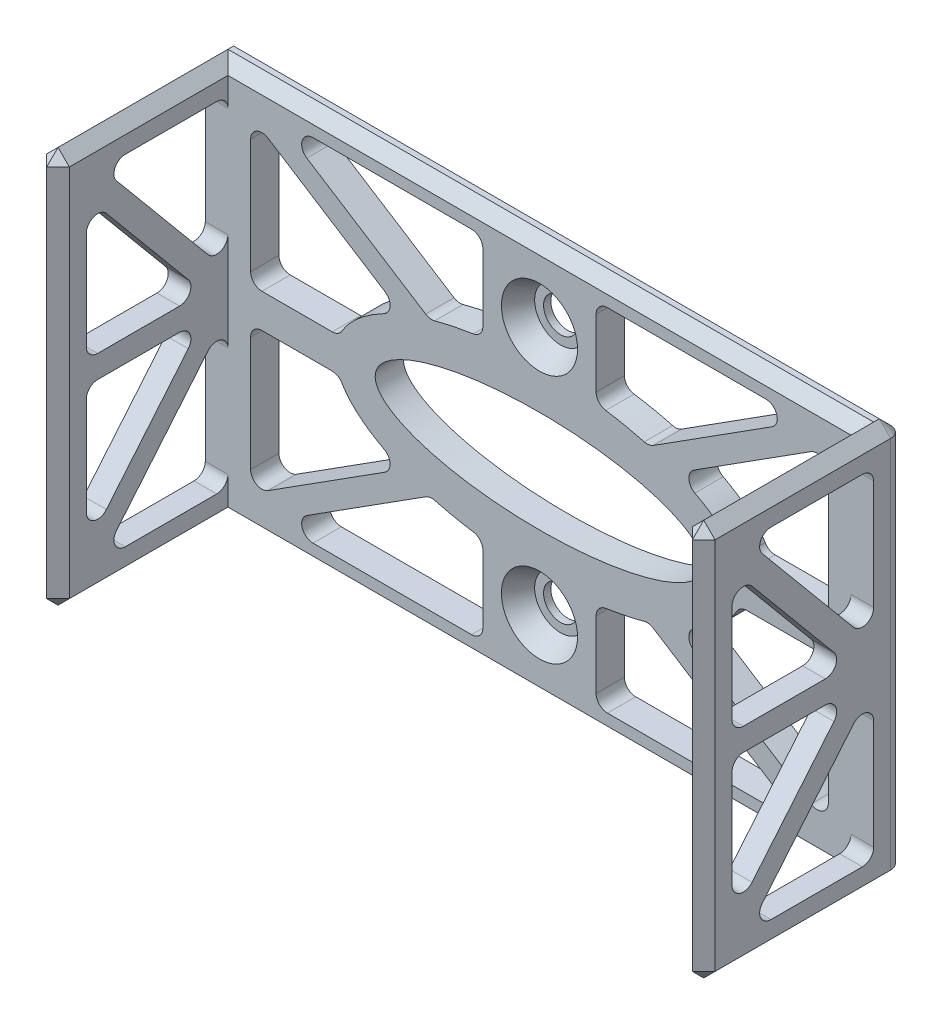
SolidWorks part; units mm, degrees
material "6061-T6 (SS)"
ref_plane "Front Plane" through (0, 0, 0) normal (0, 0, 1) x (1, 0, 0)
ref_plane "Top Plane" through (0, 0, 0) normal (0, 1, 0) x (1, 0, 0)
ref_plane "Right Plane" through (0, 0, 0) normal (1, 0, 0) x (0, 0, -1)
sketch "Sketch1" plane through (0, 0, 0) normal (0, 0, 1) x (1, 0, 0)
  line L1 (-55, 35) -> (55, 35)
  line L2 (-55, 35) -> (-55, -35)
  line L3 (-55, -35) -> (55, -35)
  line L4 (55, 35) -> (55, -35)
  line L5 (-55, 35) -> (55, -35) construction
  line L6 (-55, -35) -> (55, 35) construction
  circle A0 centre (0, 22) radius 3
  circle A1 centre (0, -22) radius 3
  point P0 (0, 0)
  dimension "D4" = 6
  dimension "D5" = 6
  dimension "D1" = 70
  dimension "D2" = 110
  dimension "D3" = 13
  dimension "D6" = 13
extrude "Boss-Extrude1" add sketch "Sketch1" along normal blind 5
sketch "Sketch2" plane through (0, 0, 5) normal (0, 0, 1) x (1, 0, 0)
  circle A0 centre (0, 22) radius 6.72
  circle A1 centre (0, -22) radius 6.72
  dimension "D1" = 13.44
  dimension "D2" = 13.44
extrude "Cut-Extrude1" cut sketch "Sketch2" against normal blind 3.72 draft 30
sketch "Sketch3" plane through (0, 0, 5) normal (0, 0, 1) x (1, 0, 0)
  line L0 (0, 0) -> (-55, 35) construction
  line L1 (0, 0) -> (-55, -35) construction
  line L2 (0, 0) -> (-13.5, 0) construction
  line L4 (-13.5, 0) -> (55, 0) construction
  line L5 (55, -35) -> (55, 35) construction
  line L6 (0, 0) -> (55, -35) construction
  line L7 (0, 0) -> (55, 35) construction
  line L8 (0, 0) -> (-55, 0) construction
  line L9 (-55, 35) -> (-55, -35) construction
  line L10 (-51, 28.8986) -> (-51, 3)
  line L11 (-51, 3) -> (-10.3022, 3)
  line L12 (-10.3022, 3) -> (-51, 28.8986)
  line L13 (-51, -3) -> (-51, -28.8986)
  line L14 (-51, -28.8986) -> (-10.3022, -3)
  line L15 (-10.3022, -3) -> (-51, -3)
  line L16 (-46.8517, 31) -> (-10, 7.5489)
  line L17 (-10, 7.5489) -> (-10, 31)
  line L18 (-10, 31) -> (-46.8517, 31)
  line L19 (-10, -7.5489) -> (-46.8517, -31)
  line L20 (-46.8517, -31) -> (-10, -31)
  line L21 (-10, -31) -> (-10, -7.5489)
  line L22 (0, 35) -> (0, -35) construction
  line L25 (-0.8631, 0.5493) -> (-0.8369, -0.5325) construction
  line L26 (55, 35) -> (-55, 35) construction
  line L27 (-55, -35) -> (55, -35) construction
  line L28 (46.8517, -31) -> (10, -31)
  line L29 (10, -7.5489) -> (46.8517, -31)
  line L30 (10, -31) -> (10, -7.5489)
  line L31 (51, -28.8986) -> (10.3022, -3)
  line L32 (51, -3) -> (51, -28.8986)
  line L33 (10.3022, -3) -> (51, -3)
  line L34 (51, 3) -> (10.3022, 3)
  line L35 (51, 28.8986) -> (51, 3)
  line L36 (10.3022, 3) -> (51, 28.8986)
  line L37 (10, 7.5489) -> (10, 31)
  line L38 (46.8517, 31) -> (10, 7.5489)
  line L39 (10, 31) -> (46.8517, 31)
  ellipse E0 centre (0, 0) end of major axis (36, 0) minor radius 16
  point P38 (-10, 19.2745)
  point P39 (-27.5, 0)
  point P40 (-30.6511, -15.9493)
  dimension "D2" = 4
  dimension "D3" = 10
  dimension "D4" = 4
  dimension "D5" = 1
  dimension "D6" = 3
  dimension "D7" = 3
  dimension "D8" = 3
  dimension "D9" = 3
  dimension "D10" = 1
  dimension "D11" = 4
  dimension "D12" = 10
  dimension "D13" = 19
  dimension "D14" = 19
extrude "Cut-Extrude2" cut sketch "Sketch3" against normal through all contours E0 L17 L18 L16 | E0 L12 L10 L11 | E0 L15 L13 L14 | E0 L19 L20 L21 | E0 L30 L28 L29 | E0 L31 L32 L33 | E0 L34 L35 L36 | E0 L38 L39 L37
sketch "Sketch5" plane through (0, 0, 5) normal (0, 0, 1) x (1, 0, 0)
  ellipse E0 centre (0, 0) end of major axis (29, 0) minor radius 9
  dimension "D1" = 7
  dimension "D2" = 7
extrude "Cut-Extrude3" cut sketch "Sketch5" against normal through all
sketch "Sketch6" plane through (-55, 0, 0) normal (-1, 0, 0) x (0, 0, 1)
  line L0 (5, -35) -> (0, -35) construction
  line L1 (0, 35) -> (35, 35)
  line L2 (0, 35) -> (0, -35)
  line L3 (0, -35) -> (35, -35)
  line L4 (35, 35) -> (35, -35)
  dimension "D1" = 35
extrude "Boss-Extrude2" add sketch "Sketch6" along normal blind 4
mirror "Mirror1" about plane through (0, 0, 0) normal (1, 0, 0) of "Boss-Extrude2"
sketch "Sketch7" plane through (59, 0, 0) normal (1, 0, 0) x (0, 0, -1)
  line L0 (-35, 35) -> (0, 35) construction
  line L1 (-27.3966, 30) -> (-5, 30)
  line L2 (-30, 26.8759) -> (-30, 2)
  line L3 (-27.3966, -30) -> (-5, -30)
  line L4 (-5, 30) -> (-5, 3.1241)
  line L5 (0, -35) -> (-35, -35) construction
  line L6 (0, 35) -> (0, -35) construction
  line L7 (-35, -35) -> (-35, 35) construction
  line L8 (-30, 30) -> (-5, 0) construction
  line L9 (-5, 0) -> (-30, -30) construction
  line L10 (-27.3966, 30) -> (-5, 3.1241)
  line L11 (-30, 26.8759) -> (-9.2701, 2)
  line L12 (-9.2701, -2) -> (-30, -26.8759)
  line L13 (-27.3966, -30) -> (-5, -3.1241)
  line L14 (-9.2701, 2) -> (-30, 2)
  line L15 (-30, -2) -> (-9.2701, -2)
  line L16 (-30, 0) -> (-5, 0) construction
  line L17 (-30, -30) -> (-35, -35) construction
  line L18 (-35, 35) -> (-30, 30) construction
  line L19 (-30, -2) -> (-30, -26.8759)
  line L20 (-5, -3.1241) -> (-5, -30)
  dimension "D1" = 5
  dimension "D2" = 5
  dimension "D3" = 5
  dimension "D4" = 5
  dimension "D5" = 2
  dimension "D6" = 2
  dimension "D7" = 2
  dimension "D8" = 2
  dimension "D9" = 2
  dimension "D10" = 2
extrude "Cut-Extrude4" cut sketch "Sketch7" against normal through all both and the other way through all
fillet "Fillet2" radius 2 58 edges at (10, -15.3703, 2.5) (10, -31, 2.5) (19.3427, -13.4943, 2.5) (46.8517, -31, 2.5) (51, -28.8986, 2.5) (24.2015, -11.845, 2.5) (35.3615, -3, 2.5) (51, -3, 2.5) (35.3615, 3, 2.5) (24.2015, 11.845, 2.5) (51, 3, 2.5) (51, 28.8986, 2.5) (10, 31, 2.5) (46.8517, 31, 2.5) (19.3427, 13.4943, 2.5) (10, 15.3703, 2.5) (-10, -31, 2.5) (-10, -15.3703, 2.5) (-19.3427, -13.4943, 2.5) (-46.8517, -31, 2.5) (-51, -28.8986, 2.5) (-24.2015, -11.845, 2.5) (-35.3615, -3, 2.5) (-51, -3, 2.5) (-51, 3, 2.5) (-35.3615, 3, 2.5) (-24.2015, 11.845, 2.5) (-51, 28.8986, 2.5) (-19.3427, 13.4943, 2.5) (-10, 15.3703, 2.5) (-10, 31, 2.5) (-46.8517, 31, 2.5) (57, -30, 5) (57, 26.8759, 30) (57, 30, 27.3966) (57, 2, 30) (57, -2, 30) (57, -26.8759, 30) (57, -30, 27.3966) (57, 3.1241, 5) (57, 2, 9.2701) (57, -3.1241, 5) (57, -2, 9.2701) (57, 30, 5) (-57, -2, 30) (-57, 30, 27.3966) (-57, 26.8759, 30) (-57, 2, 9.2701) (-57, -2, 9.2701) (-57, -3.1241, 5) (-57, 2, 30) (-57, -30, 27.3966) (-57, -26.8759, 30) (-57, -30, 5) (-57, 3.1241, 5) (-57, 30, 5) (-59, 0, 0) (59, 0, 0)
sketch "Sketch4" plane through (0, 0, 0) normal (0, 0, -1) x (-1, 0, 0)
  line L0 (57, -35) -> (-57, -35) construction
  line L1 (-15, 35) -> (15, 35)
  line L2 (-15, 35) -> (-15, -35)
  line L3 (-15, -35) -> (15, -35)
  line L4 (15, 35) -> (15, -35)
  line L5 (-15, 35) -> (15, -35) construction
  line L6 (-15, -35) -> (15, 35) construction
  point P0 (0, 0)
  dimension "D1" = 30
split line "Split Line1"
chamfer "Chamfer2" distance 2 angle 45 28 edges at (36, 35, 0) (0, 35, 0) (-36, 35, 0) (-57, 35, 35) (0, 35, 5) (57, 35, 35) (-36, -35, 0) (0, -35, 0) (36, -35, 0) (57, -35, 35) (0, -35, 5) (-57, -35, 35) (-59, -35, 18.5) (-55, -35, 20) (55, -35, 20) (59, -35, 18.5) (59, 35, 18.5) (55, 35, 20) (-55, 35, 20) (-59, 35, 18.5) (59, 0, 35) (55, 0, 35) (-59, 0, 35) (-55, 0, 35) (-58.4142, -35, 0.5858) (58.4142, -35, 0.5858) (58.4142, 35, 0.5858) (-58.4142, 35, 0.5858)
